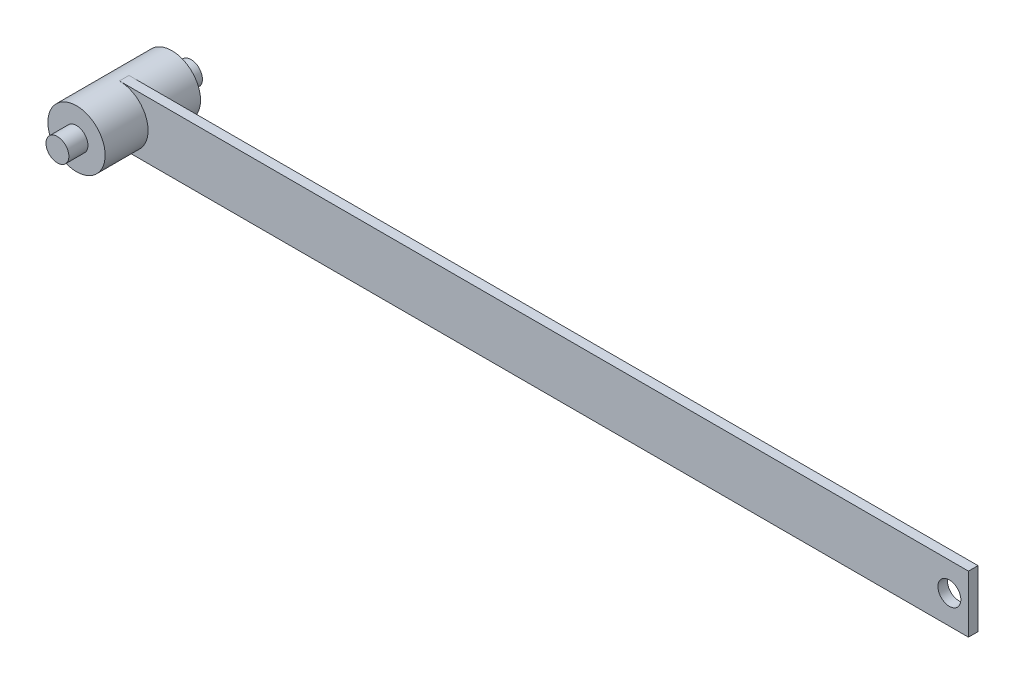
SolidWorks part; units mm, degrees
ref_plane "前视基准面" through (0, 0, 0) normal (0, 0, 1) x (1, 0, 0)
ref_plane "上视基准面" through (0, 0, 0) normal (0, 1, 0) x (1, 0, 0)
ref_plane "右视基准面" through (0, 0, 0) normal (1, 0, 0) x (0, 0, -1)
sketch "草图1" plane through (0, 0, 0) normal (0, 0, 1) x (1, 0, 0)
  line L1 (-230, 15) -> (230, 15)
  line L2 (-230, 15) -> (-230, -15)
  line L3 (-230, -15) -> (230, -15)
  line L4 (230, 15) -> (230, -15)
  line L5 (-230, 15) -> (230, -15) construction
  line L6 (-230, -15) -> (230, 15) construction
  circle A0 centre (-220, 0) radius 6
  circle A1 centre (220, 0) radius 6
  point P0 (0, 0)
  dimension "D4" = 12
  dimension "D5" = 12
  dimension "D1" = 440
  dimension "D2" = 10
  dimension "D3" = 10
  dimension "D6" = 30
extrude "凸台-拉伸1" add sketch "草图1" along normal mid plane 5
fillet "圆角1" 2 edges at (-230, 15, 0) (-230, -15, 0) type full round first side face at (0, 15, 0) second side face at (0, -15, 0) middle face at (-230, 0, 0)
sketch "草图3" plane through (0, 0, 0) normal (0, 0, 1) x (1, 0, 0)
  circle A0 centre (-215, 0) radius 15
extrude "凸台-拉伸2" add sketch "草图3" along normal mid plane 50
sketch "草图4" plane through (0, 0, 0) normal (0, 0, 1) x (1, 0, 0)
  circle A0 centre (-215, 0) radius 6
  dimension "D1" = 12
extrude "凸台-拉伸3" add sketch "草图4" along normal mid plane 70
